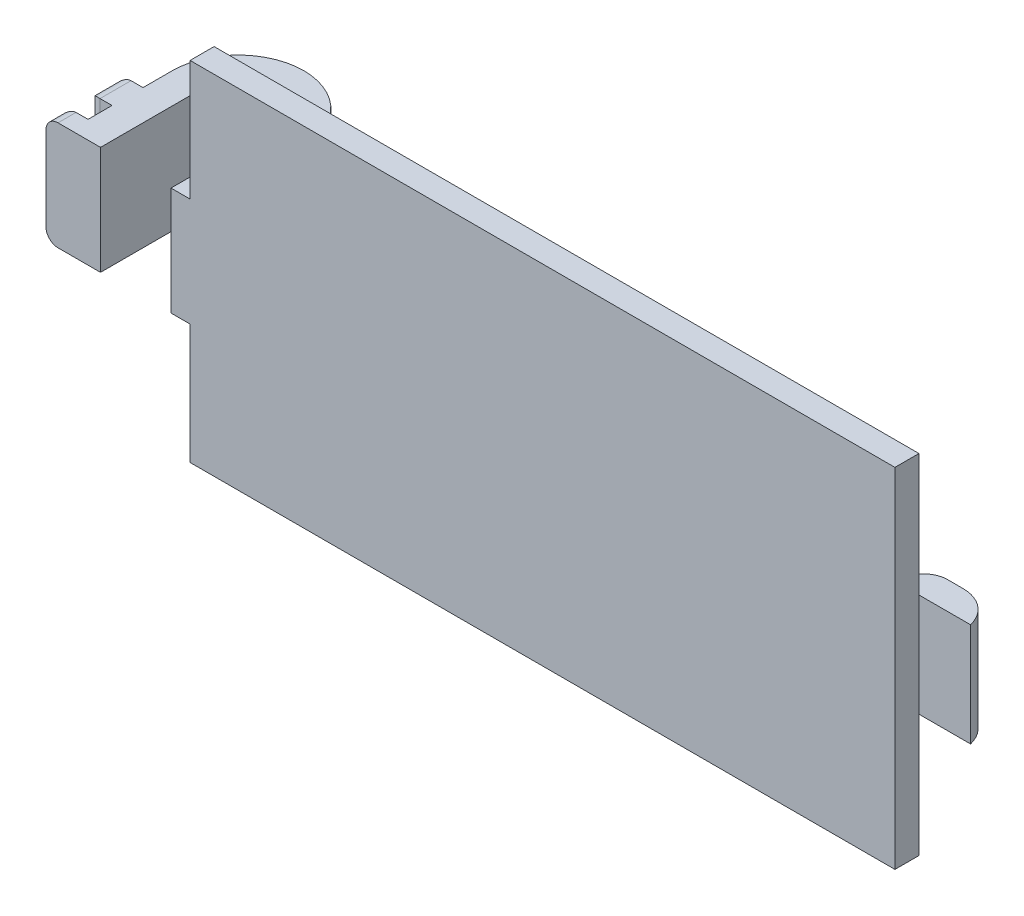
SolidWorks part; units mm, degrees
ref_plane "Front Plane" through (0, 0, 0) normal (0, 0, 1) x (1, 0, 0)
ref_plane "Top Plane" through (0, 0, 0) normal (0, 1, 0) x (1, 0, 0)
ref_plane "Right Plane" through (0, 0, 0) normal (1, 0, 0) x (0, 0, -1)
other "Graphic1"
other "Imported Graphic (Open) -1"
other "Imported Graphic (Closed) -2"
sketch "Sketch1" plane through (0, 0, 0) normal (0, 0, 1) x (1, 0, 0)
  line L0 (-13.4493, -14.4974) -> (45.2507, -14.4974)
  line L1 (-13.4493, 0.0026) -> (45.2507, 0.0026)
  line L2 (-13.4493, -14.4974) -> (-13.4493, 14.5026)
  line L3 (-13.4493, 14.5026) -> (45.2507, 14.5026)
  line L4 (45.2507, -14.4974) -> (45.2507, 14.5026)
  dimension "D1" = 14.5
extrude "Boss-Extrude1" add sketch "Sketch1" along normal blind 2 contours L0 L4 L1 L2 | L1 L4 L3 L2
sketch "Sketch2" plane through (0, 0, 2) normal (0, 0, 1) x (1, 0, 0)
  line L0 (45.2507, -14.4974) -> (45.2507, 14.5026) construction
  line L1 (43.3431, 0) -> (45.2507, 0)
  line L2 (43.3431, -4.3) -> (43.3431, 4.3)
  line L3 (43.3431, 4.3) -> (45.2507, 4.3)
  line L4 (45.2507, -4.3) -> (45.2507, 4.3)
  line L5 (43.3431, -4.3) -> (45.2507, -4.3)
  dimension "D1" = 4.3
extrude "Boss-Extrude2" add sketch "Sketch2" against normal blind 4.3 contours L2 L3 L4 L5
sketch "Sketch3" plane through (45.2507, 0, 0) normal (1, 0, 0) x (0, 0, -1)
  line L1 (0, 4.3) -> (2.3, 4.3)
  line L2 (0, 4.3) -> (0, -4.3)
  line L3 (0, -4.3) -> (2.3, -4.3)
  line L4 (2.3, 4.3) -> (2.3, -4.3)
extrude "Boss-Extrude3" add sketch "Sketch3" along normal blind 4.3
fillet "Fillet3" radius 2 1 edges at (43.3431, 0, -2.3)
sketch "Sketch4" plane through (0, 0, 0) normal (0, 0, -1) x (-1, 0, 0)
  line L0 (13.4493, -14.4974) -> (13.4493, 14.5026) construction
  line L1 (12.4996, 4.5026) -> (13.4493, 4.5026)
  line L2 (12.4996, 4.5026) -> (12.4996, -4.4974)
  line L3 (12.4996, -4.4974) -> (13.4493, -4.4974)
  line L4 (13.4493, 4.5026) -> (13.4493, -4.4974)
  dimension "D1" = 10
  dimension "D2" = 10
extrude "Boss-Extrude4" add sketch "Sketch4" along normal blind 12 contours L2 L3 L4 L1
sketch "Sketch5" plane through (-13.4493, 0, 0) normal (-1, 0, 0) x (0, 0, 1)
  line L0 (2, -14.4974) -> (2, 14.5026) construction
  line L1 (-12, 4.5026) -> (2, 4.5026)
  line L2 (-12, 4.5026) -> (-12, -4.5144)
  line L3 (-12, -4.5144) -> (2, -4.5144)
  line L4 (2, 4.5026) -> (2, -4.5144)
extrude "Boss-Extrude5" add sketch "Sketch5" along normal blind 10
sketch "Sketch6" plane through (0, 4.5026, 0) normal (0, 1, 0) x (1, 0, 0)
fillet "Fillet4" radius 5.5 2 edges at (-23.4493, -0.0059, -12) (-12.4996, 0.0026, -12)
sketch "Sketch7" plane through (0, 4.5026, 0) normal (0, 1, 0) x (1, 0, 0)
  line L0 (-17.9745, 11.9999) -> (-17.9745, -2.5421) construction
  line L1 (-12.4996, 6.5) -> (-23.4493, 6.5) construction
  line L2 (-23.4493, -2) -> (-13.4493, -2) construction
  line L3 (-20.9096, 6.5) -> (-15.0393, 6.5)
  line L4 (-20.9096, 6.5) -> (-20.9096, -2)
  line L5 (-20.9096, -2) -> (-15.0393, -2)
  line L6 (-15.0393, 6.5) -> (-15.0393, -2)
  circle A0 centre (-17.9745, 6.5) radius 2.9351
  line M4 (-23.4493, -2) -> (-13.4493, -2)
extrude "Cut-Extrude1" cut sketch "Sketch7" against normal blind 12 contours L3 A0 | L3 A0 | A0 L4 L6 M4
sketch "Sketch8" plane through (-23.4493, 0, 0) normal (-1, 0, 0) x (0, 0, 1)
  line L0 (2, 4.5026) -> (-6.5, 4.5026) construction
  line L1 (-4.0801, 4.5026) -> (-1.5, 4.5026)
  line L2 (-4.0801, 4.5026) -> (-4.0801, -4.5144)
  line L3 (-4.0801, -4.5144) -> (-1.5, -4.5144)
  line L4 (-1.5, 4.5026) -> (-1.5, -4.5144)
  line L5 (-6.5, -4.5144) -> (2, -4.5144) construction
  line L6 (2, 4.5026) -> (0, 4.5026) construction
  line L7 (2, -4.5144) -> (0.5, -4.5144)
  line L8 (2, -4.5144) -> (2, 4.5026)
  line L9 (2, 4.5026) -> (0.5, 4.5026)
  line L10 (0.5, -4.5144) -> (0.5, 4.5026)
  dimension "D1" = 3.5
  dimension "D2" = 1.5
extrude "Boss-Extrude6" add sketch "Sketch8" along normal blind 2
sketch "Sketch9" plane through (0, 0, 0) normal (0, 0, -1) x (-1, 0, 0)
  line L0 (12.5106, -2.7463) -> (10.5897, -2.7463)
  line L1 (12.4996, 4.5026) -> (10.5787, 4.5026)
  line L2 (12.4996, 4.5026) -> (12.4996, 2.8168)
  line L3 (12.4996, 2.8168) -> (10.5787, 2.8168)
  line L4 (10.5787, 4.5026) -> (10.5787, 2.8168)
  line L5 (12.5106, -2.7463) -> (12.5106, -4.4321)
  line L6 (12.5106, -4.4321) -> (10.5897, -4.4321)
  line L7 (10.5897, -2.7463) -> (10.5897, -4.4321)
sketch "Sketch10" plane through (0, 0, 0) normal (0, 0, -1) x (-1, 0, 0)
extrude "Boss-Extrude7" add sketch "Sketch9" along normal blind 3
fillet "Fillet6" radius 3 2 edges at (-10.5897, -3.5892, -3) (-10.5787, 3.6597, -3)
sketch "Sketch11" plane through (0, 0, 0) normal (0, 0, -1) x (-1, 0, 0)
  line L0 (13.4493, 4.5026) -> (13.4493, 14.5026) construction
  line L5 (13.0062, 9.9367) -> (13.4493, 9.9367)
  line L7 (13.0062, 6.6896) -> (13.4493, 6.6896)
  line L8 (13.4493, 9.9367) -> (13.4493, 6.6896)
  point P0 (0, 0)
  point P2 (0, 0)
fillet "Fillet9" radius 3 1 edges at (49.5507, 0, -2.3)
fillet "Fillet11" radius 1 4 edges at (-25.4493, 4.5026, -2.7901) (-25.4493, -0.0059, -1.5) (-25.4493, -4.5144, -2.7901) (-25.4493, -0.0059, -4.0801)
fillet "Fillet12" radius 1 3 edges at (-25.4493, -4.5144, 1.25) (-25.4493, 4.5026, 1.25) (-25.4493, -0.0059, 0.5)
